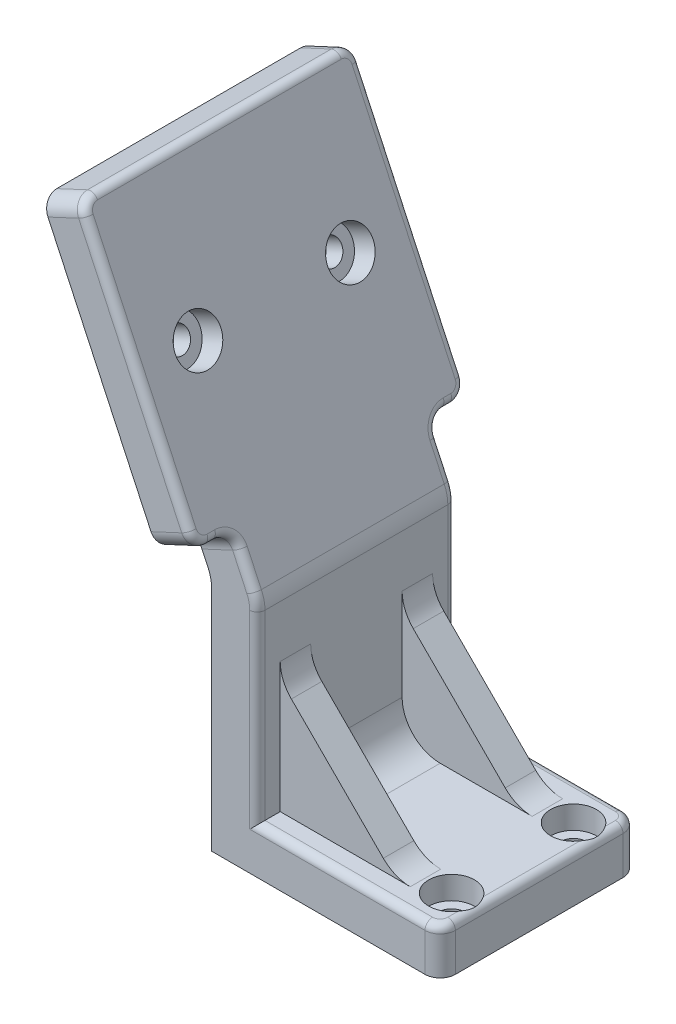
SolidWorks part; units mm, degrees
ref_plane "前视基准面" through (0, 0, 0) normal (0, 0, 1) x (1, 0, 0)
ref_plane "上视基准面" through (0, 0, 0) normal (0, 1, 0) x (1, 0, 0)
ref_plane "右视基准面" through (0, 0, 0) normal (1, 0, 0) x (0, 0, -1)
other "Configuration Table"
sketch "草图1" plane through (0, 0, 0) normal (0, 1, 0) x (1, 0, 0)
  line L0 (-15, 0) -> (15, 0) construction
  line L1 (-15, 13) -> (15, 13)
  line L2 (-15, 13) -> (-15, -13)
  line L3 (-15, -13) -> (15, -13)
  line L4 (15, 13) -> (15, -13)
  line L5 (-15, 13) -> (15, -13) construction
  line L6 (-15, -13) -> (15, 13) construction
  circle A0 centre (11.5, 8) radius 1.7
  circle A1 centre (11.5, -8) radius 1.7
  point P0 (0, 0)
  dimension "D3" = 8
  dimension "D4" = 3.4
  dimension "D5" = 3.5
  dimension "D1" = 30
  dimension "D2" = 26
extrude "凸台-拉伸1" add sketch "草图1" along normal blind 6
sketch "草图15" plane through (0, 6, 0) normal (0, 1, 0) x (1, 0, 0)
  line L0 (-15, -13) -> (15, -13) construction
  line L1 (-15, 13) -> (-9, 13)
  line L2 (-15, 13) -> (-15, -13)
  line L3 (-15, -13) -> (-9, -13)
  line L4 (-9, 13) -> (-9, -13)
  dimension "D1" = 6
extrude "凸台-拉伸4" add sketch "草图15" along normal blind 25
sketch "草图16" plane through (0, 0, 13) normal (0, 0, 1) x (1, 0, 0)
  line L0 (-9, 31) -> (-12.1847, 37.8297)
  line L1 (-12.1847, 37.8297) -> (-17.1131, 35.5315)
  line L2 (-17.1131, 35.5315) -> (-15, 31)
  line L3 (-9, 31) -> (-9, 6) construction
  line L4 (-15, 31) -> (-9, 31) construction
  line L5 (-15, 31) -> (-9, 31)
  dimension "D1" = 25
  dimension "D2" = 5
extrude "凸台-拉伸5" add sketch "草图16" against normal up to surface (26 mm away) up to face at (-3, 12.3333, -13)
sketch "草图17" plane through (-0.4472, -0.2085, 0) normal (-0.9063, -0.4226, 0) x (0, 0, 1)
  line L0 (0, 39.4348) -> (0, 57.4348) construction
  line L1 (-13, 39.4348) -> (13, 39.4348) construction
  line L2 (-18, 57.4348) -> (18, 57.4348) construction
  line L3 (-18, 75.4348) -> (18, 75.4348)
  line L4 (-18, 75.4348) -> (-18, 39.4348)
  line L5 (-18, 39.4348) -> (18, 39.4348)
  line L6 (18, 75.4348) -> (18, 39.4348)
  line L7 (-18, 75.4348) -> (18, 39.4348) construction
  line L8 (-18, 39.4348) -> (18, 75.4348) construction
  circle A0 centre (10, 57.4348) radius 1.6
  circle A1 centre (-10, 57.4348) radius 1.6
  dimension "D3" = 3.2
  dimension "D4" = 10
  dimension "D1" = 36
  dimension "D2" = 36
extrude "凸台-拉伸6" add sketch "草图17" against normal up to surface (5.4378 mm away) up to face at (-10.5924, 34.4148, 0)
fillet "圆角3" radius 2 8 edges at (-14.6489, 36.6806, -13) (-14.6489, 36.6806, 13) (-29.8632, 69.3077, 18) (-14.6489, 36.6806, 18) (-14.6489, 36.6806, -18) (-29.8632, 69.3077, -18) (15, 3, -13) (15, 3, 13)
sketch "草图18" plane through (4.4811, 2.0896, 0) normal (0.9063, 0.4226, 0) x (0, 0, -1)
  circle A0 centre (-10, 57.4348) radius 3
  circle A1 centre (10, 57.4348) radius 3
  dimension "D1" = 6
  dimension "D2" = 6
extrude "切除-拉伸4" cut sketch "草图18" against normal blind 3
sketch "草图19" plane through (0, 6, 0) normal (0, 1, 0) x (1, 0, 0)
  circle A0 centre (11.5, 8) radius 3
  circle A1 centre (11.5, -8) radius 3
  dimension "D1" = 6
  dimension "D2" = 6
extrude "切除-拉伸5" cut sketch "草图19" against normal blind 3
fillet "圆角4" radius 1 20 edges at (2, 6, -13) (14.4142, 6, -12.4142) (15, 6, 0) (14.4142, 6, 12.4142) (-10.1697, 33.5085, 13) (-11.9372, 37.2988, 13.5858) (-12.1847, 37.8297, 15.5) (-12.4323, 38.3606, 17.4142) (-19.7919, 54.1432, 18) (-27.1514, 69.9258, 17.4142) (-10.1697, 33.5085, -13) (-11.9372, 37.2988, -13.5858) (-12.1847, 37.8297, -15.5) (-12.4323, 38.3606, -17.4142) (-19.7919, 54.1432, -18) (-27.1514, 69.9258, -17.4142) (-9, 18.5, -13) (2, 6, 13) (-9, 18.5, 13) (-27.399, 70.4568, 0)
fillet "圆角6" radius 5 4 edges at (-9.2929, 30.9351, -12.7071) (-9.2929, 30.9351, 12.7071) (-9, 31, 0) (-15, 31, 0)
ref_plane "基准面2" through (0, 0, 8) normal (0, 0, 1) x (1, 0, 0)
sketch "草图20" plane through (0, 0, 8) normal (0, 0, 1) x (1, 0, 0)
  line L0 (-9, 21) -> (6, 6)
  line L1 (-9, 29.8915) -> (-9, 6) construction
  line L2 (-9, 6) -> (13, 6) construction
  line L3 (6, 6) -> (-9, 6)
  line L4 (-9, 6) -> (-9, 21)
  dimension "D1" = 15
  dimension "D2" = 15
extrude "凸台-拉伸7" add sketch "草图20" along normal mid plane 4
ref_plane "基准面3" through (0, 0, 0) normal (0, 0, -1) x (-1, 0, 0)
mirror "镜向1" about plane through (0, 0, 0) normal (0, 0, -1) of "凸台-拉伸7"
fillet "圆角7" radius 5 4 edges at (-9, 21, -8) (6, 6, -8) (6, 6, 8) (-9, 21, 8)
fillet "圆角8" radius 5 1 edges at (-9, 6, 0)
